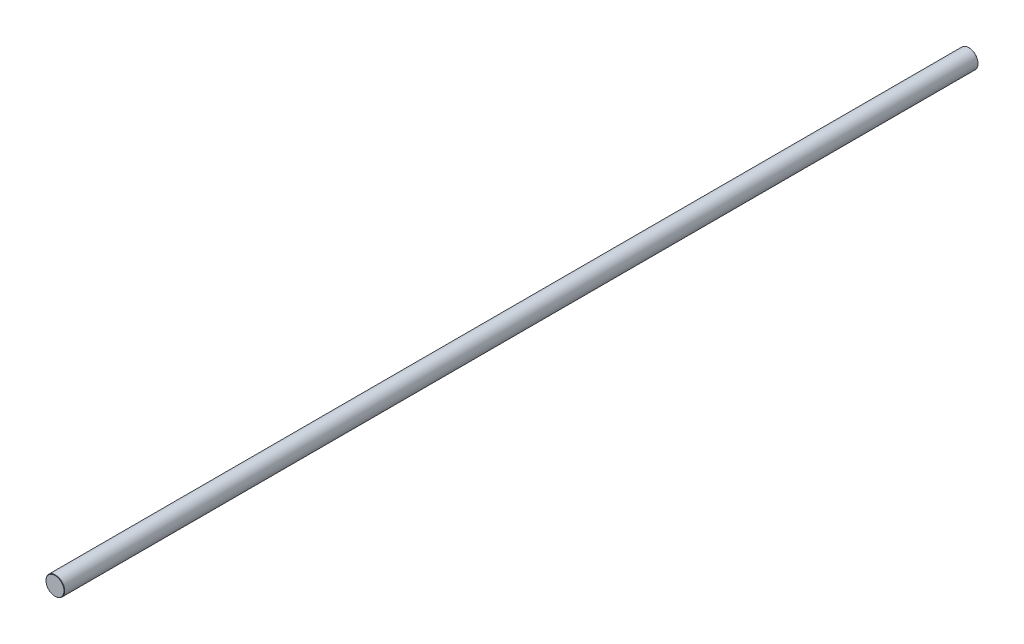
SolidWorks part; units mm, degrees
material "AISI 1045 Steel, cold drawn"
ref_plane "Front Plane" through (0, 0, 0) normal (0, 0, 1) x (1, 0, 0)
ref_plane "Top Plane" through (0, 0, 0) normal (0, 1, 0) x (1, 0, 0)
ref_plane "Right Plane" through (0, 0, 0) normal (1, 0, 0) x (0, 0, -1)
sketch "Sketch1" plane through (0, 0, 0) normal (0, 0, 1) x (1, 0, 0)
  circle A0 centre (0, 0) radius 12.5 construction
  dimension "Diameter" = 25
sketch "Sketch2" plane through (0, 0, 0) normal (1, 0, 0) x (0, 0, -1)
  line L0 (610, 0) -> (-610, 0) construction
  point P0 (-488, 0)
  point P3 (0, 0)
  point P4 (488, 0)
  point P6 (-427, 0)
  point P7 (427, 0)
  dimension "Length" = 1220
  dimension "D1" = 122
  dimension "D2" = 122
  dimension "D3" = 183
  dimension "D4" = 183
sketch "Sketch3" plane through (0, 0, 0) normal (0, 0, 1) x (1, 0, 0)
  circle A0 centre (0, 0) radius 12.5 construction
  circle A1 centre (0, 0) radius 12.5
extrude "Boss-Extrude1" add sketch "Sketch3" along normal up to vertex (610 mm away) and the other way up to vertex (610 mm away) up to point (0, 0, 610) other way up to point (0, 0, -610)
chamfer "Chamfer1" distance 0.5 angle 45 2 edges at (12.5, 0, 610) (12.5, 0, -610)
ref_axis "Axis" through (0, 0, -660) along (0, 0, 1)
equation "\"D1@Chamfer1\"=\"Diameter@Sketch1\"*.02"
equation "\"D1@Sketch2\"=\"D2@Sketch2\""
equation "\"D2@Sketch2\"=\"Length@Sketch2\"*.1"
equation "\"D3@Sketch2\"=\"Length@Sketch2\"*.15"
equation "\"D4@Sketch2\"=\"D3@Sketch2\""
